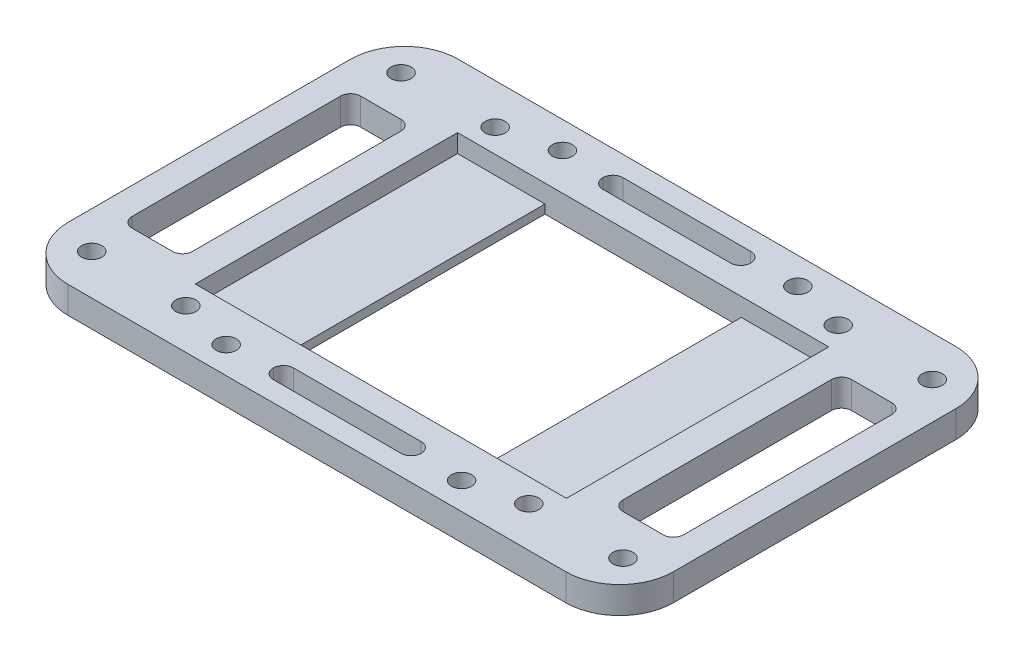
SolidWorks part; units mm, degrees
material "Tough PLA"
ref_plane "前视基准面" through (0, 0, 0) normal (0, 0, 1) x (1, 0, 0)
ref_plane "上视基准面" through (0, 0, 0) normal (0, 1, 0) x (1, 0, 0)
ref_plane "右视基准面" through (0, 0, 0) normal (1, 0, 0) x (0, 0, -1)
sketch "草图1" plane through (0, 0, 0) normal (0, 1, 0) x (1, 0, 0)
  line L0 (-25.5, 29) -> (-25.5, -29) construction
  line L1 (-45, 29) -> (45, 29)
  line L2 (-45, 29) -> (-45, -29)
  line L3 (-45, -29) -> (45, -29)
  line L4 (45, 29) -> (45, -29)
  line L5 (-45, 29) -> (45, -29) construction
  line L6 (-45, -29) -> (45, 29) construction
  line L11 (-45, 0) -> (45, 0) construction
  line L13 (39.5, 29) -> (39.5, -29) construction
  line L14 (-45, 23) -> (45, 23) construction
  line L15 (-45, -23) -> (45, -23) construction
  line L20 (25.5, 29) -> (25.5, -29) construction
  line L21 (-39.5, 29) -> (-39.5, -29) construction
  circle A0 centre (-25.5, 23) radius 1.5
  circle A1 centre (39.5, 23) radius 1.5
  circle A2 centre (-25.5, -23) radius 1.5
  circle A3 centre (39.5, -23) radius 1.5
  circle A5 centre (-39.5, 23) radius 1.5
  circle A6 centre (-39.5, -23) radius 1.5
  circle A7 centre (25.5, -23) radius 1.5
  circle A8 centre (25.5, 23) radius 1.5
  point P0 (0, 0)
  point P5 (0, 0)
  point P30 (7, 0)
  point P31 (0, 0)
  dimension "D9" = 3
  dimension "D1" = 58
  dimension "D2" = 90
  dimension "D3" = 23
  dimension "D4" = 23
  dimension "D5" = 51
  dimension "D6" = 14
  dimension "D7" = 14
  dimension "D8" = 25.5
  dimension "D11" = 2
  dimension "D10" = 2
extrude "凸台-拉伸1" add sketch "草图1" along normal blind 4
sketch "草图2" plane through (0, 4, 0) normal (0, 1, 0) x (1, 0, 0)
  line L1 (-27.6, 19.5) -> (27.6, 19.5)
  line L2 (-27.6, 19.5) -> (-27.6, -19.5)
  line L3 (-27.6, -19.5) -> (27.6, -19.5)
  line L4 (27.6, 19.5) -> (27.6, -19.5)
  line L5 (-27.6, 19.5) -> (27.6, -19.5) construction
  line L6 (-27.6, -19.5) -> (27.6, 19.5) construction
  point P0 (0, 0)
  dimension "D1" = 39
  dimension "D2" = 55.2
extrude "切除-拉伸1" cut sketch "草图2" against normal up to surface (4 mm away) up to face at (0, 0, 0)
sketch "草图5" plane through (0, 0, 0) normal (0, -1, 0) x (1, 0, 0)
  line L0 (-15.9412, -22.3) -> (-19.0588, -22.3)
  line L1 (-17.5, 25) -> (17.5, 25) construction
  line L2 (-17.5, 25) -> (-17.5, -25) construction
  line L3 (-17.5, -25) -> (17.5, -25) construction
  line L4 (17.5, 25) -> (17.5, -25) construction
  line L5 (-17.5, 25) -> (17.5, -25) construction
  line L6 (-17.5, -25) -> (17.5, 25) construction
  line L7 (-15.9412, 22.3) -> (-14.3823, 25)
  line L8 (-14.3823, 25) -> (-15.9412, 27.7)
  line L9 (-15.9412, 27.7) -> (-19.0588, 27.7)
  line L10 (-19.0588, 27.7) -> (-20.6177, 25)
  line L11 (-20.6177, 25) -> (-19.0588, 22.3)
  line L12 (-19.0588, 22.3) -> (-15.9412, 22.3)
  line L13 (19.0588, 22.3) -> (20.6177, 25)
  line L14 (20.6177, 25) -> (19.0588, 27.7)
  line L15 (19.0588, 27.7) -> (15.9412, 27.7)
  line L16 (15.9412, 27.7) -> (14.3823, 25)
  line L17 (14.3823, 25) -> (15.9412, 22.3)
  line L18 (15.9412, 22.3) -> (19.0588, 22.3)
  line L19 (-19.0588, -22.3) -> (-20.6177, -25)
  line L20 (-14.3823, -25) -> (-15.9412, -22.3)
  line L21 (-15.9412, -27.7) -> (-14.3823, -25)
  line L22 (-19.0588, -27.7) -> (-15.9412, -27.7)
  line L23 (-20.6177, -25) -> (-19.0588, -27.7)
  line L24 (19.0588, -22.3) -> (15.9412, -22.3)
  line L25 (15.9412, -22.3) -> (14.3823, -25)
  line L26 (20.6177, -25) -> (19.0588, -22.3)
  line L27 (19.0588, -27.7) -> (20.6177, -25)
  line L28 (15.9412, -27.7) -> (19.0588, -27.7)
  line L29 (14.3823, -25) -> (15.9412, -27.7)
  circle A0 centre (-17.5, 25) radius 2.7 construction
  circle A1 centre (17.5, 25) radius 2.7 construction
  circle A2 centre (-17.5, -25) radius 2.7 construction
  circle A3 centre (17.5, -25) radius 2.7 construction
  circle A8 centre (0, 0) radius 27.8 construction
  point P0 (0, 0)
  dimension "D3" = 5.4
  dimension "D5" = 55.6
  dimension "D1" = 50
  dimension "D2" = 35
  dimension "D4" = 2
sketch "草图13" plane through (0, 0, 0) normal (0, -1, 0) x (1, 0, 0)
  circle A4 centre (-17.5, 25) radius 2.7 construction
  circle A5 centre (-17.5, 25) radius 1.5
  circle A6 centre (17.5, 25) radius 1.5
  circle A7 centre (-17.5, -25) radius 1.5
  circle A8 centre (17.5, -25) radius 1.5
  dimension "D1" = 3
  dimension "D2" = 2
  dimension "D3" = 2
extrude "切除-拉伸6" cut sketch "草图13" against normal up to surface (4 mm away) up to face at (0, 4, 0)
sketch "草图14" plane through (0, 4, 0) normal (0, 1, 0) x (1, 0, 0)
  line L0 (-45, 0) -> (45, 0) construction
  line L1 (32, 17) -> (41, 17)
  line L2 (32, 17) -> (32, -17)
  line L3 (32, -17) -> (41, -17)
  line L4 (41, 17) -> (41, -17)
  line L5 (-41, 17) -> (-32, 17)
  line L6 (-41, 17) -> (-41, -17)
  line L7 (-41, -17) -> (-32, -17)
  line L8 (-32, 17) -> (-32, -17)
  line L9 (-45, 29) -> (-45, -29) construction
  line L10 (45, -29) -> (45, 29) construction
  line L11 (0, 29) -> (0, -29) construction
  line L12 (45, 29) -> (-45, 29) construction
  line L13 (-45, -29) -> (45, -29) construction
  line L15 (-11, 26) -> (11, 26)
  line L16 (-11, 26) -> (-11, 23)
  line L17 (-11, 23) -> (11, 23)
  line L18 (11, 26) -> (11, 23)
  line L19 (11, -26) -> (11, -23)
  line L20 (-11, -26) -> (-11, -23)
  line L21 (-11, -23) -> (11, -23)
  line L22 (-11, -26) -> (11, -26)
  point P14 (-41, 0)
  point P15 (41, 0)
  point P27 (0, 26)
  dimension "D1" = 32
  dimension "D2" = 32
  dimension "D3" = 4
  dimension "D4" = 4
  dimension "D5" = 34
  dimension "D6" = 3
  dimension "D7" = 3
  dimension "D8" = 22
extrude "切除-拉伸7" cut sketch "草图14" against normal up to surface (4 mm away) up to face at (17.5, 0, 23.5)
fillet "圆角1" radius 8 4 edges at (-45, 2, -29) (45, 2, -29) (45, 2, 29) (-45, 2, 29)
fillet "圆角2" radius 1.5 16 edges at (11, 2, 23) (-11, 2, 23) (11, 2, 26) (-11, 2, 26) (-11, 2, -23) (11, 2, -23) (11, 2, -26) (-11, 2, -26) (41, 2, 17) (32, 2, 17) (41, 2, -17) (32, 2, -17) (-41, 2, 17) (-32, 2, 17) (-32, 2, -17) (-41, 2, -17)
sketch "草图18" plane through (0, 0, 0) normal (0, -1, 0) x (1, 0, 0)
  line L0 (-30, 20) -> (-30, -20)
  line L25 (-30, 20) -> (-14.6, 20)
  line L27 (-30, -20) -> (-14.6, -20)
  line L28 (-14.6, 20) -> (-14.6, -20)
  line L29 (30, 20) -> (14.6, 20)
  line L30 (30, 20) -> (30, -20)
  line L31 (30, -20) -> (14.6, -20)
  line L32 (14.6, 20) -> (14.6, -20)
  point P0 (0, 0)
  dimension "D1" = 14.6
  dimension "D2" = 30
  dimension "D3" = 14.6
  dimension "D4" = 30
  dimension "D5" = 20
  dimension "D6" = 20
extrude "凸台-拉伸4" add sketch "草图18" against normal blind 1.3 separate body
